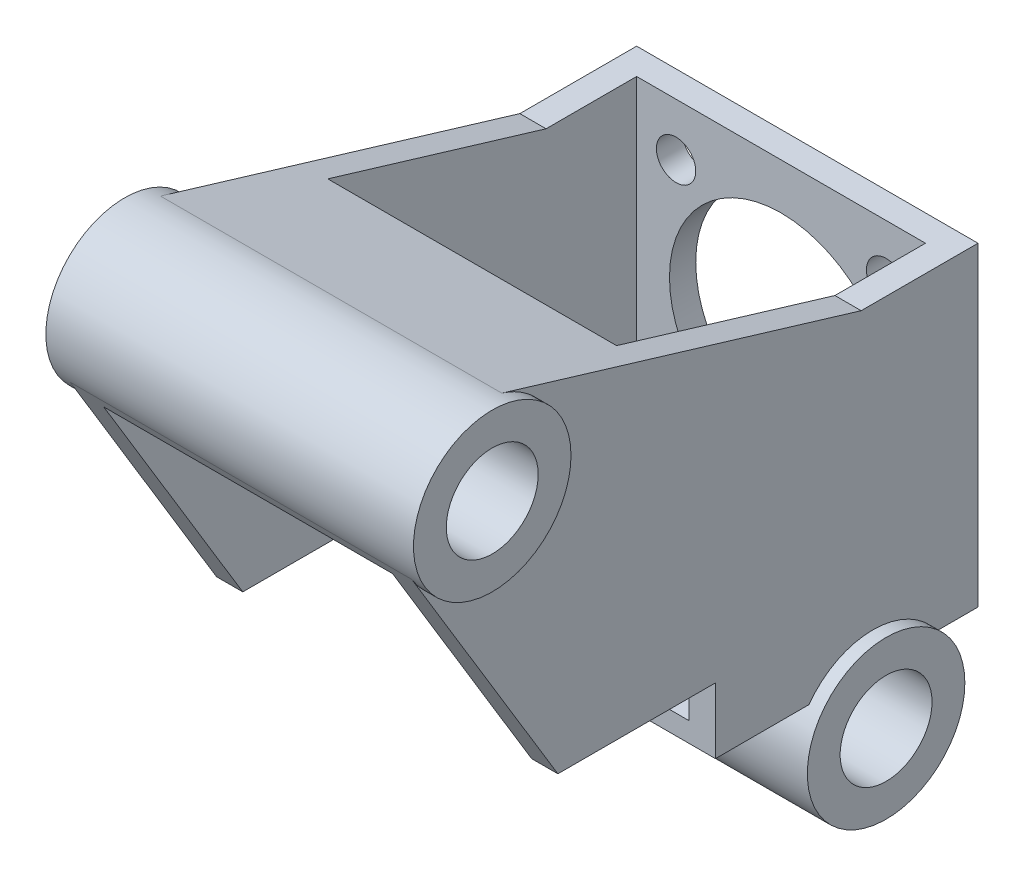
SolidWorks part; units mm, degrees
ref_plane "Front Plane" through (0, 0, 0) normal (0, 0, 1) x (1, 0, 0)
ref_plane "Top Plane" through (0, 0, 0) normal (0, 1, 0) x (1, 0, 0)
ref_plane "Right Plane" through (0, 0, 0) normal (1, 0, 0) x (0, 0, -1)
sketch "Sketch1" plane through (0, 0, 0) normal (1, 0, 0) x (0, 0, -1)
  circle A0 centre (-30, 15) radius 3.5
  circle A1 centre (0, -15) radius 3.5
  circle A2 centre (-30, 15) radius 6
  circle A3 centre (0, -15) radius 6
  dimension "D1" = 7
  dimension "D2" = 12
  dimension "D3" = 30
  dimension "D4" = 30
  dimension "D5" = 15
extrude "Boss-Extrude1" add sketch "Sketch1" along normal mid plane 28
sketch "Sketch2" plane through (0, 0, 0) normal (1, 0, 0) x (0, 0, -1)
  line L0 (8, 12.5) -> (8, -11.5)
  line L1 (8, -11.5) -> (-12, -11.5)
  line L2 (-12, -11.5) -> (-12, -6.5)
  line L4 (-0.8995, 12.5) -> (8, 12.5)
  line L5 (-12, -6.5) -> (-24, -6.5)
  line L6 (-24, -6.5) -> (-35.133, 11.8931)
  line L8 (-0.8995, 12.5) -> (-28.2694, 20.745)
  circle A0 centre (0, -15) radius 3.5 construction
  circle A1 centre (0, -15) radius 3.5 construction
  circle A2 centre (-30, 15) radius 6 construction
  arc A3 (-28.2694, 20.745) -> (-35.133, 11.8931) centre (-30, 15) cw
  dimension "D4" = 8
  dimension "D1" = 24
  dimension "D2" = 20
  dimension "D3" = 32
  dimension "D5" = 5
extrude "Boss-Extrude2" add sketch "Sketch2" along normal mid plane 26
sketch "Sketch4" plane through (0, 0, 0) normal (1, 0, 0) x (0, 0, -1)
  line L0 (8, -11.5) -> (8, 12.5) construction
  line L1 (6, 12.5) -> (-0.8995, 12.5)
  line L2 (6, 12.5) -> (6, -10)
  line L3 (6, -10) -> (-36, -10)
  line L4 (-36, 11) -> (-36, -10)
  line L5 (4.8734, -11.5) -> (8, -11.5) construction
  line L6 (8, 12.5) -> (-0.8995, 12.5) construction
  line L7 (-0.8995, 12.5) -> (-17.5296, 17.5097)
  line L8 (-17.5296, 11) -> (-36, 11)
  line L10 (-0.8995, 12.5) -> (-28.2694, 20.745) construction
  line L11 (-17.5296, 11) -> (-17.5296, 17.5097)
  circle A1 centre (-30, 15) radius 6 construction
  dimension "D1" = 2
  dimension "D2" = 21
  dimension "D4" = 1.5
extrude "Cut-Extrude2" cut sketch "Sketch4" along normal mid plane 22
sketch "Sketch5" plane through (0, 0, -8) normal (0, 0, -1) x (-1, 0, 0)
  line L0 (-13, 0.5) -> (13, 0.5) construction
  line L1 (-13, -11.5) -> (-13, 12.5) construction
  line L2 (13, -11.5) -> (13, 12.5) construction
  line L3 (0, 12.5) -> (0, -11.5) construction
  line L4 (-13, -11.5) -> (13, -11.5) construction
  line L5 (-13, 12.5) -> (13, 12.5) construction
  circle A0 centre (0, 0.5) radius 8.5
  circle A1 centre (-8, 8.5) radius 1.5
  circle A2 centre (-8, -7.5) radius 1.5
  circle A3 centre (8, 8.5) radius 1.5
  circle A4 centre (8, -7.5) radius 1.5
  point P8 (0, 0.5)
  point P9 (0, 0.5)
  dimension "D1" = 17
  dimension "D3" = 16
  dimension "D4" = 3
  dimension "D2" = 16
extrude "Cut-Extrude3" cut sketch "Sketch5" against normal up to surface (2 mm away) up to face at (0, 1.25, -6)
ref_axis "Top Crossbeam Axis" through (14, 15, 30) along (-1, 0, 0)
ref_axis "Bottom Crossbeam Axis" through (14, -15, 0) along (-1, 0, 0)
